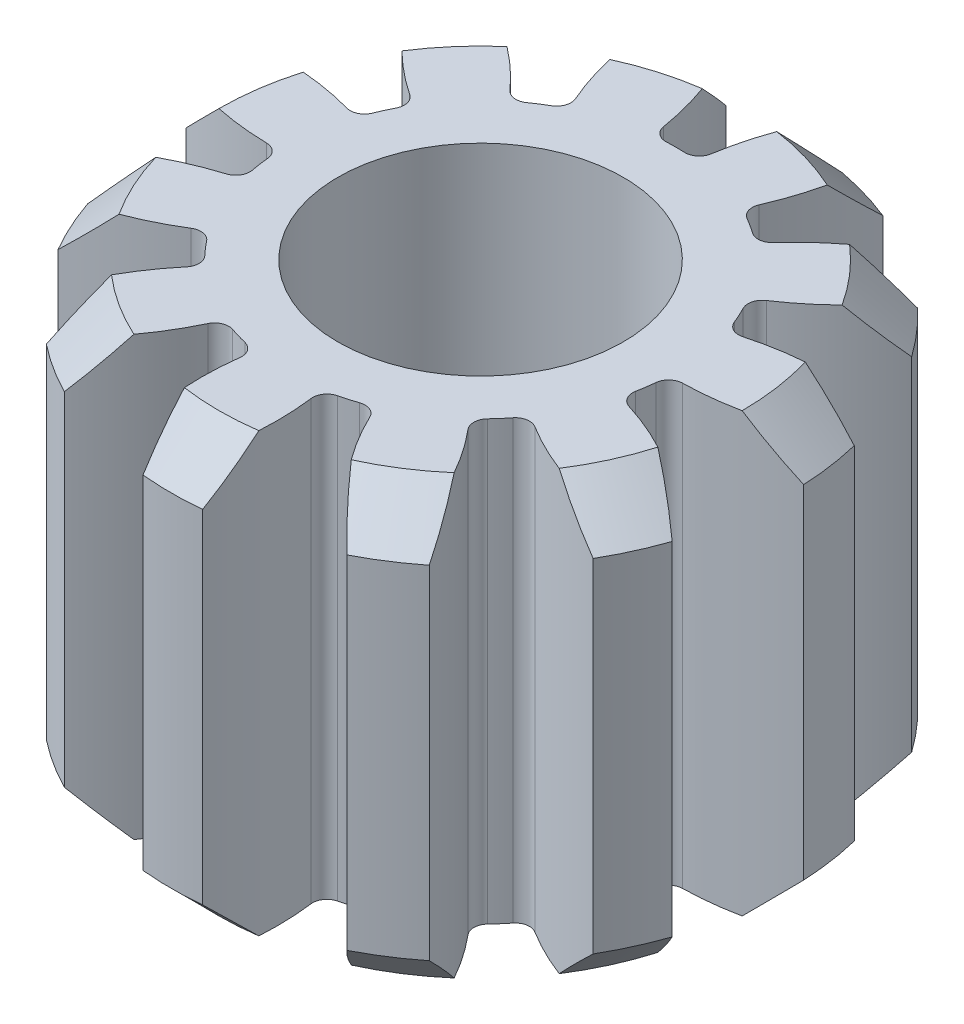
SolidWorks part; units mm, degrees
ref_plane "Front Plane" through (0, 0, 0) normal (0, 0, 1) x (1, 0, 0)
ref_plane "Top Plane" through (0, 0, 0) normal (0, 1, 0) x (1, 0, 0)
ref_plane "Right Plane" through (0, 0, 0) normal (1, 0, 0) x (0, 0, -1)
sketch "Sketch1" plane through (0, 0, 0) normal (0, 1, 0) x (1, 0, 0)
  circle A0 centre (0, 0) radius 1.375 construction
  circle A1 centre (0, 0) radius 1.625
  dimension "D1" = 2.75
  dimension "D2" = 3.25
extrude "Boss-Extrude1" add sketch "Sketch1" along normal blind 2.3
sketch "Sketch2" plane through (0, 2.3, 0) normal (0, 1, 0) x (1, 0, 0)
  line L0 (0, 0) -> (0, 1.625) construction
  line L1 (0, 0) -> (0.8785, 1.367) construction
  line L2 (0, 0) -> (0.4578, 1.5592) construction
  line L3 (-0.1152, 1.0185) -> (0, 0) construction
  line L4 (-0.1957, 1.361) -> (0.1957, 1.361) construction
  line L5 (0.1957, 1.361) -> (0.5712, 1.2507) construction
  line L6 (-0.2827, 1.6002) -> (0, 0.8234) construction
  circle A0 centre (0, 0) radius 1.125 construction
  circle A2 centre (0, 0) radius 1.625 construction
  arc A3 (-0.1152, 1.0185) -> (-0.3052, 1.5961) centre (-1.5972, 0.8509) ccw
  arc A4 (0.1152, 1.0185) -> (0.3052, 1.5961) centre (1.5972, 0.8509) cw
  circle A5 centre (0, 0) radius 1.375 construction
  arc A7 (0.1152, 1.0185) -> (-0.1152, 1.0185) centre (0, 0) ccw
  arc A8 (0.3052, 1.5961) -> (-0.3052, 1.5961) centre (0, 0) ccw
  dimension "D1" = 32.727
  dimension "D2" = 0.5
  dimension "D4" = 20
extrude "Cut-Extrude1" cut sketch "Sketch2" against normal through all
fillet "Fillet1" radius 0.075 2 edges at (0.1152, 1.15, -1.0185) (-0.1152, 1.15, -1.0185)
chamfer "Chamfer1" distance 0.25 2 edges at (0, 0, 1.625) (0, 2.3, 1.625)
pattern_circular "CirPattern2" count 11 over 360 about axis through (0, 2.3, 0) along (0, -1, 0) of "Cut-Extrude1", "Fillet1" reverse direction yes
sketch "Sketch3" plane through (0, 2.3, 0) normal (0, 1, 0) x (1, 0, 0)
  circle A0 centre (0, 0) radius 0.75
  dimension "D1" = 1.5
extrude "Cut-Extrude2" cut sketch "Sketch3" against normal through all
equation "\"Module of gear\"= 0.25"
equation "\"Number of teeth\"= 11"
equation "\"Pressure Angle\"= 20"
equation "\"D1@Sketch1\"=\"Module of gear\" * \"Number of teeth\""
equation "\"D2@Sketch1\"=(\"Number of teeth\" + 2) * \"Module of gear\""
equation "\"D1@Sketch2\"=360 / \"Number of teeth\""
equation "\"D2@Sketch2\"=\"Module of gear\" * 2"
equation "\"D4@Sketch2\"=\"Pressure Angle\""
equation "\"D1@Fillet1\"=0.3 * \"Module of gear\""
equation "\"D1@Chamfer1\"=\"Module of gear\""
equation "\"D1@CirPattern2\"=\"Number of teeth\""
